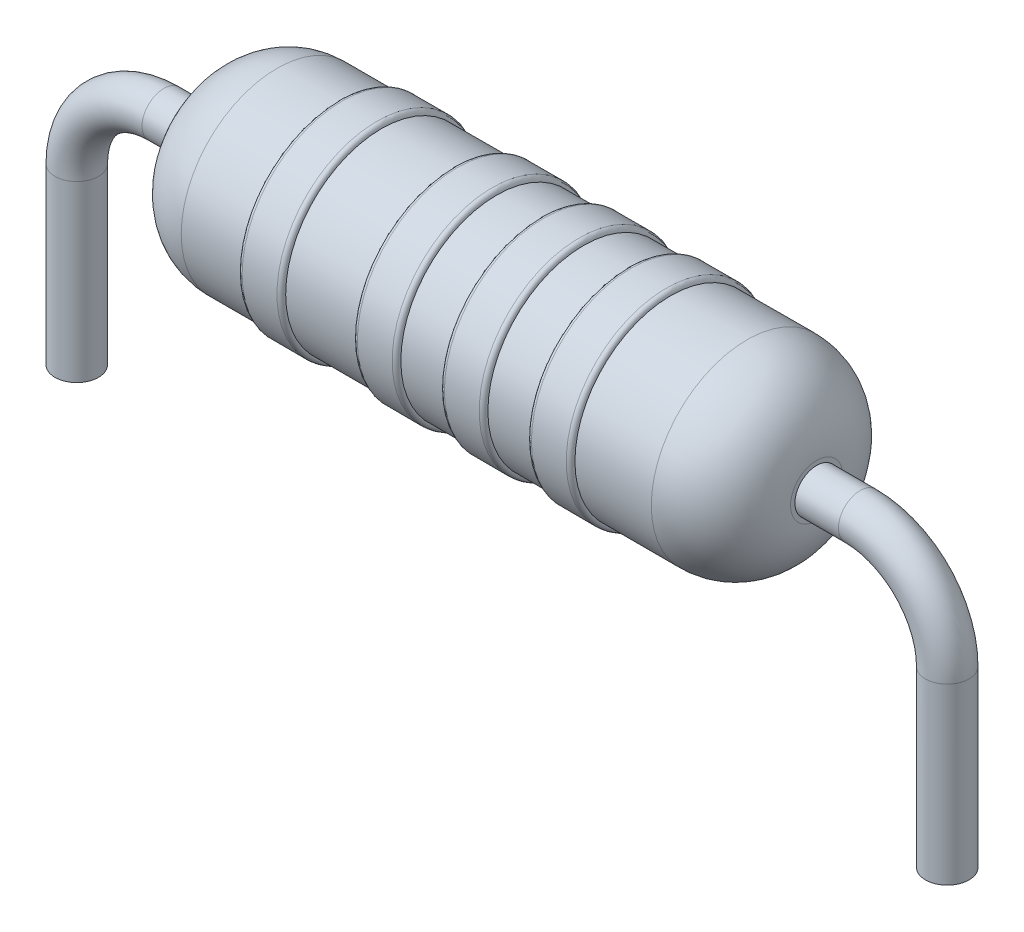
SolidWorks part; units mm, degrees
ref_plane "Face" through (0, 0, 0) normal (0, 0, 1) x (1, 0, 0)
ref_plane "Dessus" through (0, 0, 0) normal (0, 1, 0) x (1, 0, 0)
ref_plane "Droite" through (0, 0, 0) normal (1, 0, 0) x (0, 0, -1)
sketch "Esquisse1" plane through (0, 0, 0) normal (0, 0, 1) x (1, 0, 0)
  line L0 (-54.2687, 0) -> (62.1733, 0) construction
  line L1 (-48.4922, 1.1) -> (45.7559, 1.1) construction
  line L2 (-3.5, -1.6411) -> (-3.5, 4.3175) construction
  line L3 (0, -1.0268) -> (0, 4.1947) construction
  line L4 (3.5, 3.6009) -> (3.5, -1.9687) construction
  line L5 (-3.5, 0) -> (-3.5, 0.3)
  line L6 (-2.7, 1.1) -> (2.7, 1.1)
  line L7 (3.5, 0.3) -> (3.5, 0)
  line L8 (3.5, 0) -> (-3.5, 0)
  arc A0 (-2.7, 1.1) -> (-3.5, 0.3) centre (-2.7, 0.3) ccw
  arc A1 (3.5, 0.3) -> (2.7, 1.1) centre (2.7, 0.3) ccw
revolve "Base-Révolution" add sketch "Esquisse1" angle 360 about L0
sketch "Esquisse2" plane through (0, 0, 0) normal (0, 0, 1) x (1, 0, 0)
  line L0 (-3.3896, 1.15) -> (3.161, 1.15) construction
  line L1 (-2, 1.3889) -> (-2, -0.1179) construction
  line L2 (-1.5, 1.4925) -> (-1.5, -0.2136) construction
  line L3 (4.3262, 0) -> (-3.8651, 0) construction
  line L4 (1.323, 0) -> (1.823, 0)
  line L5 (0.323, 0) -> (0.823, 0)
  line L6 (-0.677, 1.15) -> (-0.677, 0)
  line L7 (0.323, 1.15) -> (0.323, 0)
  line L8 (1.323, 1.15) -> (1.323, 0)
  line L9 (-0.177, 1.15) -> (-0.177, 0)
  line L10 (0.823, 1.15) -> (0.823, 0)
  line L11 (1.823, 1.15) -> (1.823, 0)
  line L12 (-0.677, 0) -> (-0.177, 0)
  line L13 (-0.677, 1.15) -> (-0.177, 1.15)
  line L14 (0.323, 1.15) -> (0.823, 1.15)
  line L15 (1.323, 1.15) -> (1.823, 1.15)
  line L16 (-2, 1.15) -> (-1.5, 1.15)
  line L17 (-1.5, 1.15) -> (-1.5, 0)
  line L18 (-1.5, 0) -> (-2, 0)
  line L19 (-2, 0) -> (-2, 1.15)
revolve "Boss.-Révol.1" add sketch "Esquisse2" angle 360 about L3
fillet "Congé1" radius 0.05 8 edges at (-2, 0, -1.15) (-1.5, 0, -1.15) (-0.677, 0, -1.15) (-0.177, 0, -1.15) (0.323, 0, -1.15) (0.823, 0, -1.15) (1.323, 0, -1.15) (1.823, 0, -1.15)
sketch "Esquisse3" plane through (-3.5, 0, 0) normal (-1, 0, 0) x (0, 0, 1)
  circle A0 centre (0, 0) radius 0.25
sketch "Esquisse4" plane through (0, 0, 0) normal (0, 0, 1) x (1, 0, 0)
  line L0 (-2.8835, 0) -> (-5.8186, 0) construction
  line L1 (0, -2.524) -> (0, 3.2043) construction
  line L2 (-5.9326, -3) -> (3.6667, -3) construction
  line L3 (-5, 1.6795) -> (-5, -13.4876) construction
  line L4 (-3, 0) -> (-4, 0)
  line L5 (-5, -1) -> (-5, -3)
  arc A0 (-4, 0) -> (-5, -1) centre (-4, -1) ccw
  dimension "D1" = 3
  dimension "D2" = 5
sweep "Balayage1" add profiles "Esquisse3" path "Esquisse4"
ref_plane "Plan1" through (0, 0, 0) normal (1, 0, 0) x (0, 0, -1)
mirror "Symétrie1" about plane through (0, 0, 0) normal (1, 0, 0) of "Balayage1"
